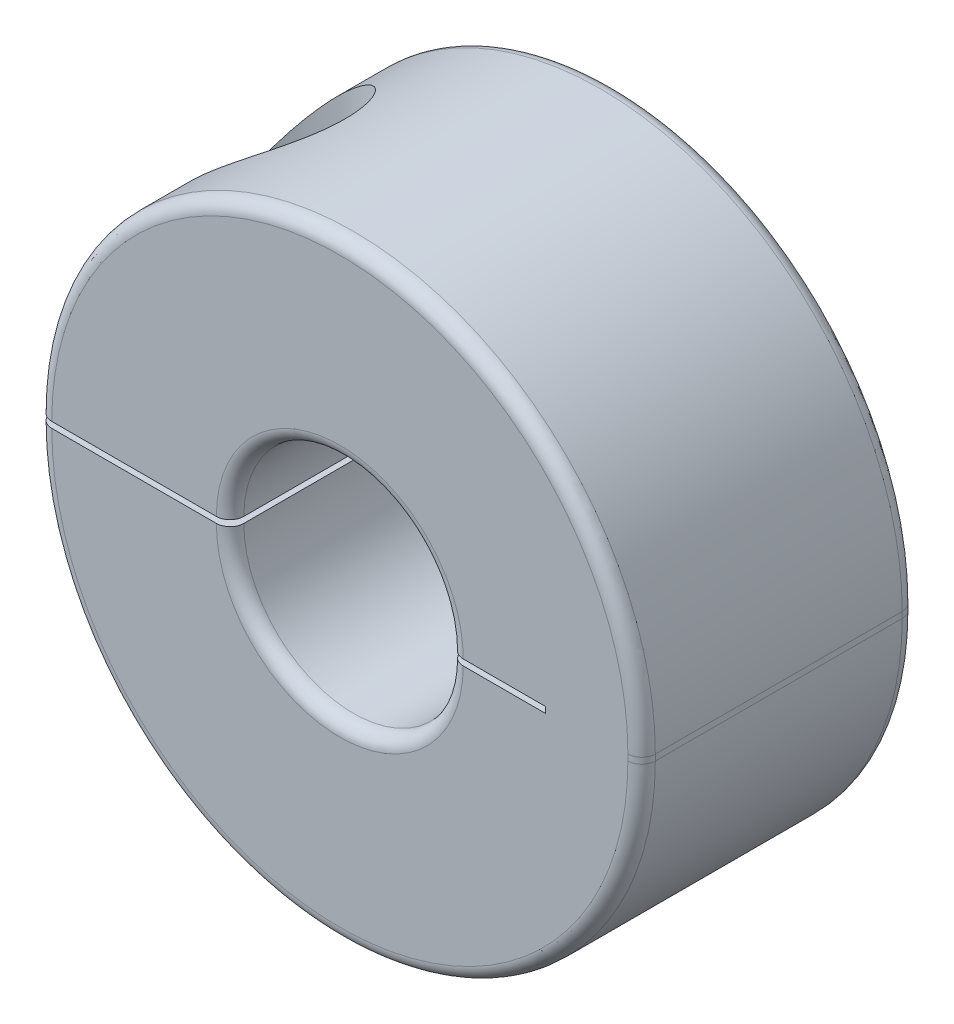
SolidWorks part; units mm, degrees
ref_plane "Front Plane" through (0, 0, 0) normal (0, 0, 1) x (1, 0, 0)
ref_plane "Top Plane" through (0, 0, 0) normal (0, 1, 0) x (1, 0, 0)
ref_plane "Right Plane" through (0, 0, 0) normal (1, 0, 0) x (0, 0, -1)
sketch "Sketch1" plane through (0, 0, 0) normal (0, 0, 1) x (1, 0, 0)
  line L0 (-8.7312, 0) -> (-3.175, 0) construction
  line L1 (-8.7313, 0.0873) -> (-3.175, 0.0873)
  line L2 (-8.7313, -0.0873) -> (-3.175, -0.0873)
  line L3 (3.175, 0.0873) -> (8.7313, 0.0873) construction
  line L4 (3.175, -0.0873) -> (8.7313, -0.0873) construction
  line L5 (0, 0) -> (0, 8.7313) construction
  line L6 (8.7313, 0.0873) -> (8.7313, -0.0873)
  line L7 (3.175, 0.0873) -> (5.9531, 0.0873)
  line L8 (5.9531, 0.0873) -> (5.9531, -0.0873)
  line L10 (5.9531, -0.0873) -> (3.175, -0.0873)
  circle A0 centre (0, 0) radius 8.7313 construction
  circle A1 centre (0, 0) radius 3.175 construction
  arc A2 (-8.7313, 0.0873) -> (8.7313, 0.0873) centre (0, 0.0873) cw
  arc A3 (-8.7313, -0.0873) -> (8.7313, -0.0873) centre (0, -0.0873) ccw
  arc A4 (-3.175, 0.0873) -> (3.175, 0.0873) centre (0, 0.0873) cw
  arc A5 (-3.175, -0.0873) -> (3.175, -0.0873) centre (0, -0.0873) ccw
  point P4 (8.7312, 0)
  dimension "Bore Dia" = 6.35
  dimension "OD" = 17.4625
  dimension "Separation" = 0.1746
extrude "Extrude1" add sketch "Sketch1" along normal mid plane 7.9375
sketch "Sketch4" plane through (0, 0, 0) normal (0, 0, 1) x (1, 0, 0)
  line L0 (-5.9531, 8.8186) -> (-3.8195, 8.8186)
  line L1 (-3.8195, 8.8186) -> (-3.8195, 0.7985)
  line L2 (-3.8195, 0.7985) -> (-4.5307, 0.7985)
  line L3 (-4.5307, 0.7985) -> (-4.5307, -8.8186)
  line L4 (-4.5307, -8.8186) -> (-5.9531, -8.8186)
  line L5 (-5.9531, -8.8186) -> (-5.9531, 8.8186)
  line L6 (-3.8195, 3.6433) -> (-8.0867, 3.6433) construction
  line L7 (-5.9531, 8.8186) -> (-5.9531, 11.3586) construction
  line L8 (-3.8195, 8.8186) -> (0, 8.8186) construction
  line L9 (0, -8.8186) -> (-4.5307, -8.8186) construction
  line L10 (-8.7313, 0) -> (-3.175, 0) construction
  line L11 (-8.7313, 0.0873) -> (-3.175, 0.0873) construction
  circle A0 centre (0, 0) radius 8.7313 construction
  arc A1 (8.7313, 0.0873) -> (-8.7313, 0.0873) centre (0, 0.0873) ccw construction
  circle A2 centre (0, 0) radius 3.175 construction
  arc A3 (-8.7313, -0.0873) -> (8.7313, -0.0873) centre (0, -0.0873) ccw construction
  point P13 (-5.9531, 0)
  point P19 (-5.9531, 0)
  point P20 (-5.9531, 3.6433)
  dimension "D1" = 2.8448
  dimension "D2" = 5.5563
  dimension "D3" = 0.7112
  dimension "D4" = 4.2672
  dimension "D5" = 2.54
  dimension "Screw Dia" = 2.8448
revolve "Cut-Revolve1" cut sketch "Sketch4" angle 360 about L5
sketch "Sketch6" plane through (0, 0, 0) normal (0, 0, 1) x (1, 0, 0)
  line L0 (-5.9531, 3.6433) -> (-3.8195, 3.6433)
  line L1 (-3.8195, 3.6433) -> (-8.0867, 3.6433) construction
  line L2 (-3.8195, 3.6433) -> (-3.8195, 0.7985)
  line L3 (-3.8195, 0.7985) -> (-4.5307, 0.7985)
  line L4 (-4.5307, 0.7985) -> (-4.5307, -4.8911)
  line L5 (-4.5307, 0.7985) -> (-4.5307, -8.8186) construction
  line L6 (-4.5307, -4.8911) -> (-5.9531, -4.8911)
  line L7 (-5.9531, -8.8186) -> (-5.9531, 8.8186) construction
  line L8 (-5.9531, -4.8911) -> (-5.9531, 3.6433)
  line L9 (-4.5307, -4.8911) -> (-7.3755, -4.8911) construction
  dimension "Head Ht" = 2.8448
  dimension "Screw Lg" = 8.5344
revolve "Revolve1" add sketch "Sketch6" angle 360 about L8
sketch "Sketch7" plane through (0, 3.6433, 0) normal (0, 1, 0) x (-1, 0, 0)
  line L1 (5.9531, -1.314) -> (7.091, -0.657)
  line L2 (7.091, -0.657) -> (7.091, 0.657)
  line L3 (7.091, 0.657) -> (5.9531, 1.314)
  line L4 (5.9531, 1.314) -> (4.8152, 0.657)
  line L5 (4.8152, 0.657) -> (4.8152, -0.657)
  line L6 (4.8152, -0.657) -> (5.9531, -1.314)
  circle A0 centre (5.9531, 0) radius 1.1379 construction
  dimension "D1" = 2.2758
extrude "Cut-Extrude2" cut sketch "Sketch7" against normal blind 1.4224
fillet "Fillet1" radius 0.3969 8 edges at (0, 3.2623, -3.9688) (0, 3.2623, 3.9688) (0, 8.8186, -3.9688) (0, 8.8186, 3.9688) (0, -8.8186, -3.9688) (0, -8.8186, 3.9688) (8.7313, 0, -3.9688) (8.7313, 0, 3.9688)
fillet "Fillet2" radius 0.3969 2 edges at (0, -3.2623, -3.9688) (0, -3.2623, 3.9688)
chamfer "Chamfer2" distance 0.254 angle 45 1 edges at (-5.9531, 3.6433, -2.1336)
equation "\"D1@Sketch4\" = \"Screw Dia@Sketch4\""
equation "\"D4@Sketch4\" = \"Screw Dia@Sketch4\"*1.5"
equation "\"D1@Sketch7\" = \"Screw Dia@Sketch4\"*.8"
equation "\"D1@Cut-Extrude2\" = \"Head Ht@Sketch6\"/2"
equation "\"D3@Sketch4\" = \"D1@Sketch4\"*.25"
equation "\"D1@Fillet1\" = \"Width@Extrude1\"*.05"
equation "\"D1@Fillet2\" = \"D1@Fillet1\""
equation "\"Screw Lg@Sketch6\" = \"Head Ht@Sketch6\"*3"
equation "\"Separation@Sketch1\" = \"OD@Sketch1\"*.01"
